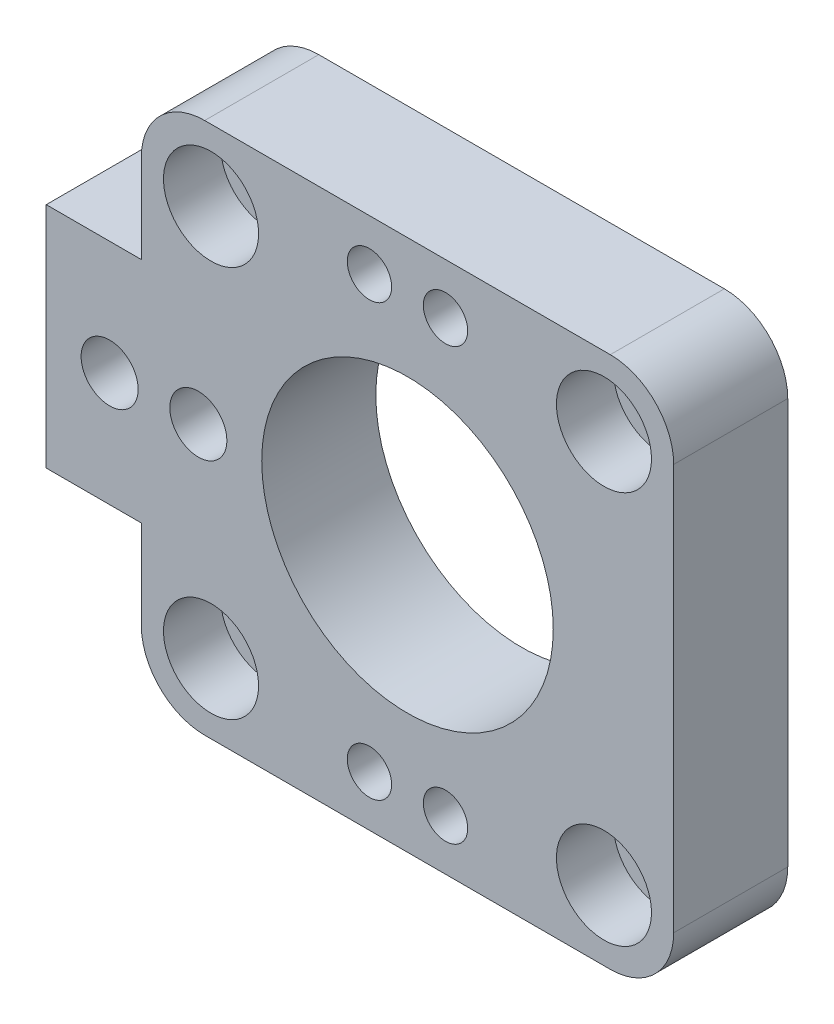
SolidWorks part; units mm, degrees
ref_plane "Plan de face" through (0, 0, 0) normal (0, 0, 1) x (1, 0, 0)
ref_plane "Plan de dessus" through (0, 0, 0) normal (0, 1, 0) x (1, 0, 0)
ref_plane "Plan de droite" through (0, 0, 0) normal (1, 0, 0) x (0, 0, -1)
sketch "Esquisse1" plane through (0, 0, 0) normal (0, 0, 1) x (1, 0, 0)
  line L1 (0, 0) -> (-42, 0)
  line L2 (0, 0) -> (0, -42)
  line L3 (0, -42) -> (-42, -42)
  line L4 (-42, 0) -> (-42, -42)
  line L5 (-42, -30) -> (-49.5, -30)
  line L6 (-42, -30) -> (-42, -12)
  line L7 (-42, -12) -> (-49.5, -12)
  line L8 (-49.5, -30) -> (-49.5, -12)
  circle A0 centre (-36.5, -5.611) radius 1.75
  circle A1 centre (-5.5, -5.5) radius 1.75
  circle A2 centre (-5.5, -36.5) radius 1.75
  circle A3 centre (-36.5, -36.5) radius 1.75
  circle A4 centre (-21, -21) radius 11.5
  dimension "D3" = 3.5
  dimension "D4" = 3.5
  dimension "D5" = 3.5
  dimension "D6" = 3.5
  dimension "D17" = 23
  dimension "D1" = 42
  dimension "D2" = 42
  dimension "D7" = 5.5
  dimension "D8" = 5.5
  dimension "D9" = 5.5
  dimension "D10" = 5.5
  dimension "D11" = 5.5
  dimension "D12" = 5.611
  dimension "D13" = 5.5
  dimension "D14" = 5.5
  dimension "D15" = 21
  dimension "D16" = 21
  dimension "D18" = 18
  dimension "D19" = 28.5
  dimension "D20" = 12
extrude "Boss.-Extru.1" add sketch "Esquisse1" along normal blind 9 contours L1 L4 L3 L2 A4 A3 A2 A1 A0 | L8 L5 L4 L7 region at (-0.594, -21, 0) region at (-45.75, -21, 0)
sketch "Esquisse9" plane through (0, 0, 9) normal (0, 0, 1) x (1, 0, 0)
  line L0 (-42, -30) -> (-49.5, -30) construction
  line L1 (-49.5, -30) -> (-49.5, -12) construction
  circle A0 centre (-44.5, -21) radius 2.25
  circle A1 centre (-37.5, -21) radius 2.25
  dimension "D1" = 4.5
  dimension "D2" = 4.5
  dimension "D3" = 9
  dimension "D4" = 9
  dimension "D5" = 5
  dimension "D6" = 12
extrude "Enlèv. mat.-Extru.2" cut sketch "Esquisse9" against normal blind 17 contours A1 | A0
sketch "Esquisse10" plane through (0, 0, 0) normal (0, 0, -1) x (-1, 0, 0)
  line L0 (49.5, -30) -> (49.5, -12) construction
  line L1 (44.5, -25.3301) -> (48.25, -23.1651)
  line L2 (48.25, -23.1651) -> (48.25, -18.8349)
  line L3 (48.25, -18.8349) -> (44.5, -16.6699)
  line L4 (44.5, -16.6699) -> (40.75, -18.8349)
  line L5 (40.75, -18.8349) -> (40.75, -23.1651)
  line L6 (40.75, -23.1651) -> (44.5, -25.3301)
  line L7 (37.5, -25.3301) -> (41.25, -23.1651)
  line L8 (41.25, -23.1651) -> (41.25, -18.8349)
  line L9 (41.25, -18.8349) -> (37.5, -16.6699)
  line L10 (37.5, -16.6699) -> (33.75, -18.8349)
  line L11 (33.75, -18.8349) -> (33.75, -23.1651)
  line L12 (33.75, -23.1651) -> (37.5, -25.3301)
  circle A2 centre (44.5, -21) radius 3.75 construction
  circle A3 centre (37.5, -21) radius 3.75 construction
  circle M1 centre (44.5, -21) radius 2.25
  circle M2 centre (37.5, -21) radius 2.25
  dimension "D3" = 7.5
  dimension "D4" = 7.5
  dimension "D5" = 0
  dimension "D6" = 0
extrude "Enlèv. mat.-Extru.3" cut sketch "Esquisse10" against normal blind 4.5 contours M2 | M1 | L8 L9 L10 L11 L12 L7 region at (-42.8065, -24.222, 0) region at (-39.1935, -24.222, 0)
sketch "Esquisse11" plane through (0, 0, 9) normal (0, 0, 1) x (1, 0, 0)
  circle A0 centre (-36.5, -5.611) radius 3.75
  circle A1 centre (-5.5, -5.5) radius 3.75
  circle A2 centre (-5.5, -36.5) radius 3.75
  circle A3 centre (-36.5, -36.5) radius 3.75
  dimension "D1" = 7.5
  dimension "D2" = 7.5
  dimension "D3" = 7.5
  dimension "D4" = 7.5
extrude "Enlèv. mat.-Extru.4" cut sketch "Esquisse11" against normal blind 4.5
fillet "Congé1" radius 5 4 edges at (-42, 0, 4.5) (0, 0, 4.5) (0, -42, 4.5) (-42, -42, 4.5)
sketch "Esquisse12" plane through (0, 0, 9) normal (0, 0, 1) x (1, 0, 0)
  line L1 (-5, -42) -> (-37, -42) construction
  line L2 (0, -5) -> (0, -37) construction
  line L3 (-42, -30) -> (-42, -37) construction
  line L4 (-5, 0) -> (-37, 0) construction
  circle A0 centre (-24, -38) radius 1.75
  circle A2 centre (-18, -38) radius 1.75
  circle A3 centre (-24, -4) radius 1.75
  circle A4 centre (-18, -4) radius 1.75
  dimension "D1" = 3.5
  dimension "D2" = 3.5
  dimension "D9" = 3.5
  dimension "D10" = 3.5
  dimension "D3" = 4
  dimension "D4" = 4
  dimension "D5" = 6
  dimension "D6" = 42
  dimension "D7" = 18
  dimension "D8" = 18
  dimension "D11" = 18
  dimension "D12" = 6
  dimension "D13" = 4
  dimension "D14" = 4
extrude "Enlèv. mat.-Extru.5" cut sketch "Esquisse12" against normal blind 10
sketch "Esquisse14" plane through (0, 0, 0) normal (0, 0, -1) x (-1, 0, 0)
  line L1 (27, -39.7321) -> (27, -36.2679)
  line L2 (27, -36.2679) -> (24, -34.5359)
  line L3 (24, -34.5359) -> (21, -36.2679)
  line L4 (21, -36.2679) -> (21, -39.7321)
  line L5 (21, -39.7321) -> (24, -41.4641)
  line L6 (24, -41.4641) -> (27, -39.7321)
  line L7 (21, -39.7321) -> (21, -36.2679)
  line L8 (21, -36.2679) -> (18, -34.5359)
  line L9 (18, -34.5359) -> (15, -36.2679)
  line L10 (15, -36.2679) -> (15, -39.7321)
  line L11 (15, -39.7321) -> (18, -41.4641)
  line L12 (18, -41.4641) -> (21, -39.7321)
  line L13 (27, -5.7321) -> (27, -2.2679)
  line L14 (27, -2.2679) -> (24, -0.5359)
  line L15 (24, -0.5359) -> (21, -2.2679)
  line L16 (21, -2.2679) -> (21, -5.7321)
  line L17 (21, -5.7321) -> (24, -7.4641)
  line L18 (24, -7.4641) -> (27, -5.7321)
  line L19 (21, -2.2679) -> (18, -0.5359)
  line L20 (18, -0.5359) -> (15, -2.2679)
  line L21 (15, -2.2679) -> (15, -5.7321)
  line L22 (15, -5.7321) -> (18, -7.4641)
  line L23 (18, -7.4641) -> (21, -5.7321)
  line L24 (21, -5.7321) -> (21, -2.2679)
  circle A2 centre (24, -38) radius 3 construction
  circle A6 centre (24, -4) radius 3 construction
  circle A7 centre (18, -4) radius 3 construction
  point P1 (0, 0)
  point P3 (0, 0)
  circle M1 centre (24, -38) radius 1.75
  circle M2 centre (24, -4) radius 1.75
  circle M3 centre (18, -4) radius 1.75
  circle M4 centre (18, -38) radius 1.75
  dimension "D1" = 6
  dimension "D2" = 360
  dimension "D3" = 0
  dimension "D4" = 0
  dimension "D7" = 0
  dimension "D5" = 6
  dimension "D6" = 6
  dimension "D8" = 6
extrude "Enlèv. mat.-Extru.8" cut sketch "Esquisse14" against normal blind 4.5 contours M3 | M2 | M1 | M4 region at (-25.4542, -40.5187, 0) region at (-19.4542, -40.5187, 0) region at (-25.4542, -6.5187, 0) region at (-19.4542, -6.5187, 0)
